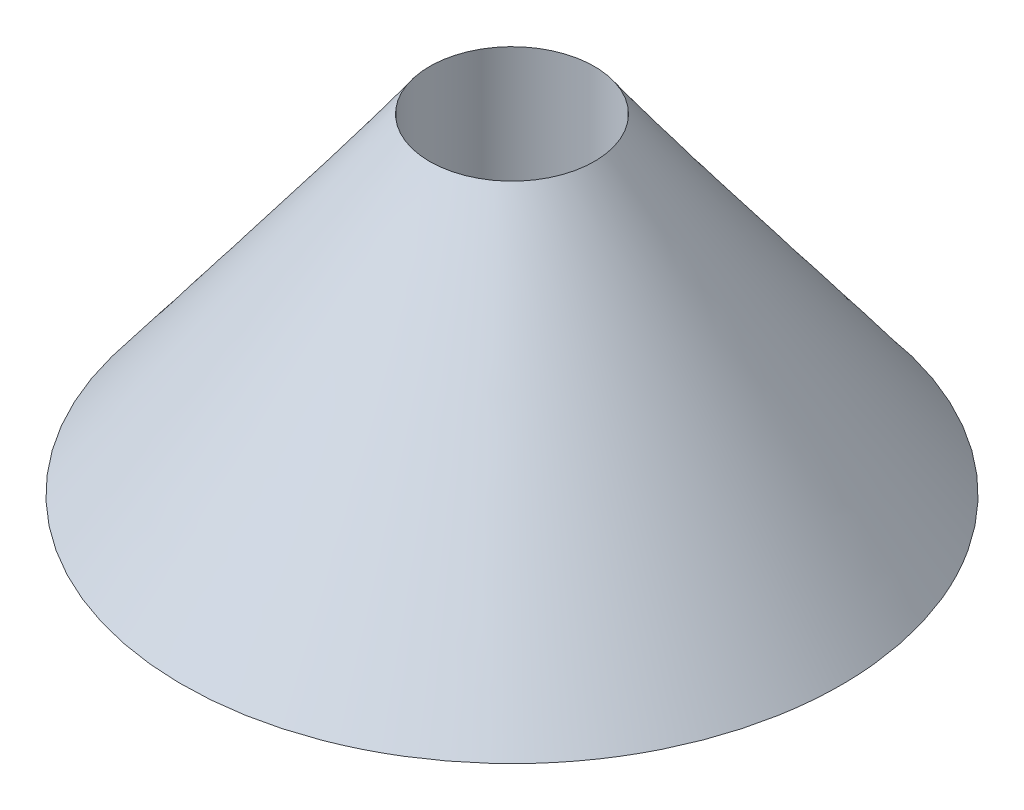
SolidWorks part; units mm, degrees
ref_plane "Front Plane" through (0, 0, 0) normal (0, 0, 1) x (1, 0, 0)
ref_plane "Top Plane" through (0, 0, 0) normal (0, 1, 0) x (1, 0, 0)
ref_plane "Right Plane" through (0, 0, 0) normal (1, 0, 0) x (0, 0, -1)
ref_axis "X" through (-88.99, 0, 0) along (1, 0, 0)
ref_axis "Y" through (0, 55, 0) along (0, -1, 0)
ref_axis "Z" through (0, 0, -88.99) along (0, 0, 1)
sketch "Sketch1" plane through (0, 0, 0) normal (0, 1, 0) x (1, 0, 0)
  circle A0 centre (0, 0) radius 4
  dimension "D1" = 8
ref_plane "Plane1" through (0, 4, 0) normal (0, 1, 0) x (1, 0, 0)
sketch "Sketch2" plane through (0, 4, 0) normal (0, 1, 0) x (1, 0, 0)
  circle A0 centre (0, 0) radius 1
  dimension "D1" = 2
loft "Loft1" add profiles "Sketch1", "Sketch2" connector at (-3.8011, 0, -1.2456) connector at (-0.8008, 4, -0.5989)
sketch "Sketch4" plane through (0, 4, 0) normal (0, 1, 0) x (1, 0, 0)
  circle A0 centre (0, 0) radius 1
  circle A1 centre (0, 0) radius 1 construction
extrude "Cut-Extrude1" cut sketch "Sketch4" against normal blind 2
